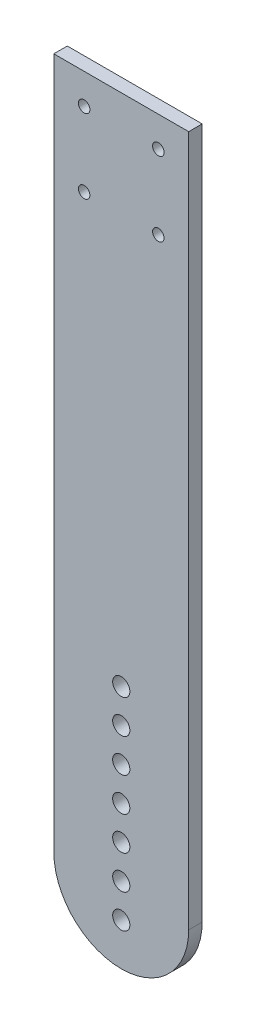
SolidWorks part; units mm, degrees
other "Markup1"
sketch "Sketch7" plane through (-20, 225, -2) normal (-0.1146, 0.1086, -0.9875) x (-0.991, 0.0573, 0.1213)
ref_plane "Front Plane" through (0, 0, 0) normal (0, 0, 1) x (1, 0, 0)
ref_plane "Top Plane" through (0, 0, 0) normal (0, 1, 0) x (1, 0, 0)
ref_plane "Right Plane" through (0, 0, 0) normal (1, 0, 0) x (0, 0, -1)
sketch "Sketch1" plane through (0, 0, 0) normal (0, 1, 0) x (1, 0, 0)
  line L1 (-20, 2) -> (20, 2)
  line L2 (-20, 2) -> (-20, -2)
  line L3 (-20, -2) -> (20, -2)
  line L4 (20, 2) -> (20, -2)
  line L5 (-20, 2) -> (20, -2) construction
  line L6 (-20, -2) -> (20, 2) construction
  point P0 (0, 0)
extrude "Boss-Extrude1" add sketch "Sketch1" along normal blind 225
fillet "Fillet1" radius 20 2 edges at (-20, 0, 0) (20, 0, 0)
sketch "Sketch2" plane through (0, 0, 2) normal (0, 0, 1) x (1, 0, 0)
  circle A0 centre (0, 12.5) radius 2.55
  dimension "D1" = 12.5
extrude "Cut-Extrude1" cut sketch "Sketch2" against normal through all
pattern_linear "LPattern1" count 7 spacing 10 along (0, 1, 0) of "Cut-Extrude1"
sketch "Sketch8" plane through (0, 0, -2) normal (0, 0, -1) x (-1, 0, 0)
  line L0 (-20, 225) -> (20, 225) construction
  line L1 (-20, 225) -> (-20, 20) construction
  line L2 (20, 225) -> (20, 20) construction
  line L3 (-20, 185) -> (20, 185) construction
  circle A0 centre (-11, 216) radius 1.7
  circle A1 centre (11, 216) radius 1.7
  circle A2 centre (-11, 194) radius 1.7
  circle A3 centre (11, 194) radius 1.7
  dimension "D1" = 9
  dimension "D3" = 9
  dimension "D5" = 3.4
  dimension "D2" = 9
  dimension "D4" = 9
  dimension "D6" = 40
  dimension "D7" = 9
extrude "Cut-Extrude4" cut sketch "Sketch8" against normal through all
